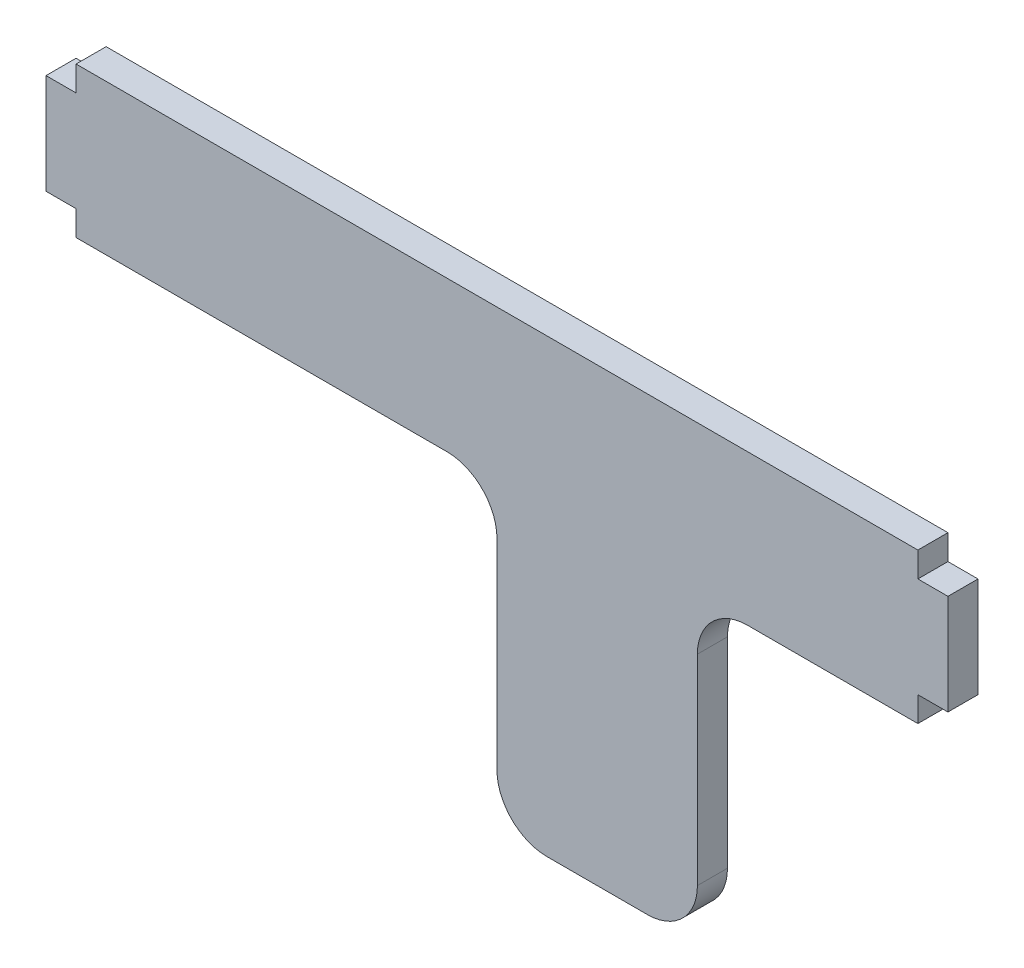
SolidWorks part; units mm, degrees
ref_plane "Plano frontal" through (0, 0, 0) normal (0, 0, 1) x (1, 0, 0)
ref_plane "Plano superior" through (0, 0, 0) normal (0, 1, 0) x (1, 0, 0)
ref_plane "Plano direito" through (0, 0, 0) normal (1, 0, 0) x (0, 0, -1)
sketch "Esboço1" plane through (0, 0, 0) normal (0, 0, 1) x (1, 0, 0)
  line L0 (0, 0) -> (0, 7.5) construction
  line L1 (42, -7.5) -> (-42, -7.5)
  line L2 (42, -7.5) -> (42, 7.5)
  line L3 (42, 7.5) -> (-42, 7.5)
  line L4 (-42, -7.5) -> (-42, 7.5)
  line L5 (42, -7.5) -> (-42, 7.5) construction
  line L6 (42, 7.5) -> (-42, -7.5) construction
  line L7 (20, -37.5) -> (0, -37.5)
  line L8 (20, -37.5) -> (20, -7.5)
  line L9 (20, -7.5) -> (0, -7.5)
  line L10 (0, -37.5) -> (0, -7.5)
  line L11 (20, -37.5) -> (0, -7.5) construction
  line L12 (20, -7.5) -> (0, -37.5) construction
  line L13 (-45, -5) -> (-42, -5)
  line L14 (-45, -5) -> (-45, 5)
  line L15 (-45, 5) -> (-42, 5)
  line L16 (-42, -5) -> (-42, 5)
  line L17 (-45, -5) -> (-42, 5) construction
  line L18 (-45, 5) -> (-42, -5) construction
  line L19 (45, 5) -> (42, 5)
  line L20 (42, -5) -> (42, 5)
  line L21 (45, -5) -> (42, -5)
  line L22 (45, -5) -> (45, 5)
  point P0 (0, 0)
  point P6 (10, -22.5)
  point P12 (-43.5, 0)
  point P22 (0, 0)
  point P23 (0, 0)
  dimension "D1" = 84
  dimension "D2" = 30
  dimension "D3" = 15
  dimension "D4" = 20
  dimension "D5" = 3
  dimension "D6" = 10
  dimension "D7" = 35
extrude "Ressalto-extrusão1" add sketch "Esboço1" along normal blind 3 contours L4 L1 L2 L3 | L10 L7 L8 L1 | L21 L22 L19 L2 | L15 L14 L13 L4 region at (0, 0, 0) region at (10, -22.5, 0) region at (43.5, 0, 0) region at (-43.5, 0, 0)
fillet "Filete1" radius 5 4 edges at (20, -37.5, 1.5) (0, -37.5, 1.5) (0, -7.5, 1.5) (20, -7.5, 1.5)
